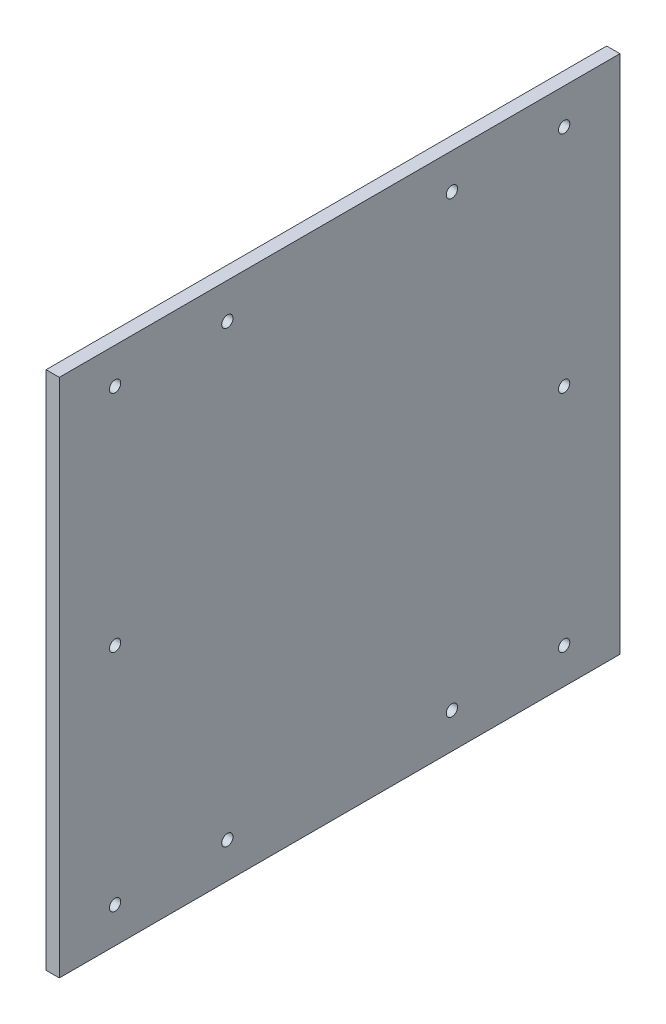
SolidWorks part; units mm, degrees
ref_plane "Front Plane" through (0, 0, 0) normal (1, 0, 0) x (0, 1, 0)
ref_plane "Top Plane" through (0, 0, 0) normal (0, 0, 1) x (0, 1, 0)
ref_plane "Right Plane" through (0, 0, 0) normal (0, 1, 0) x (-1, 0, 0)
sketch "Sketch1" plane through (0, 0, 0) normal (1, 0, 0) x (0, 1, 0)
  line L0 (-101.6, 126.85) -> (-101.6, -126.85) construction
  line L1 (-117.7, -126.85) -> (117.7, -126.85)
  line L2 (-117.7, -126.85) -> (-117.7, 126.85)
  line L3 (-117.7, 126.85) -> (117.7, 126.85)
  line L4 (117.7, -126.85) -> (117.7, 126.85)
  line L5 (-117.7, -126.85) -> (117.7, 126.85) construction
  line L6 (-117.7, 126.85) -> (117.7, -126.85) construction
  line L7 (101.6, 126.85) -> (101.6, -126.85) construction
  line L8 (-117.7, 101.6) -> (117.7, 101.6) construction
  line L9 (-117.7, -101.6) -> (117.7, -101.6) construction
  line L10 (0, 126.85) -> (0, -126.85) construction
  line L11 (-117.7, 0) -> (117.7, 0) construction
  line L12 (-117.7, -50.8) -> (117.7, -50.8) construction
  line L13 (-117.7, 50.8) -> (117.7, 50.8) construction
  circle A0 centre (-101.6, 101.6) radius 2.555
  circle A1 centre (101.6, 101.6) radius 2.555
  circle A2 centre (-101.6, -101.6) radius 2.555
  circle A3 centre (101.6, -101.6) radius 2.555
  circle A4 centre (0, -101.6) radius 2.555
  circle A5 centre (0, 101.6) radius 2.555
  circle A6 centre (-101.6, -50.8) radius 2.555
  circle A7 centre (101.6, -50.8) radius 2.555
  circle A8 centre (101.6, 50.8) radius 2.555
  circle A9 centre (-101.6, 50.8) radius 2.555
  point P0 (0, 0)
  dimension "D3" = 5.11
  dimension "D8" = 5.11
  dimension "D9" = 50.8
  dimension "D11" = 5.11
  dimension "D1" = 235.4
  dimension "D2" = 253.7
  dimension "D4" = 203.2
  dimension "D5" = 101.6
  dimension "D6" = 203.2
  dimension "D7" = 101.6
  dimension "D10" = 50.8
extrude "Boss-Extrude1" add sketch "Sketch1" along normal blind 6 contours L1 L4 L3 L2
extrude "Cut-Extrude1" cut sketch "Sketch1<3>" along normal blind 10 contours A0 | A1 | A3 | A2 | A6 | A9 | A8 | A7 | A5 | A4
sketch "Sketch1<3>" plane through (0, 0, 0) normal (1, 0, 0) x (0, 1, 0) same geometry as "Sketch1"
